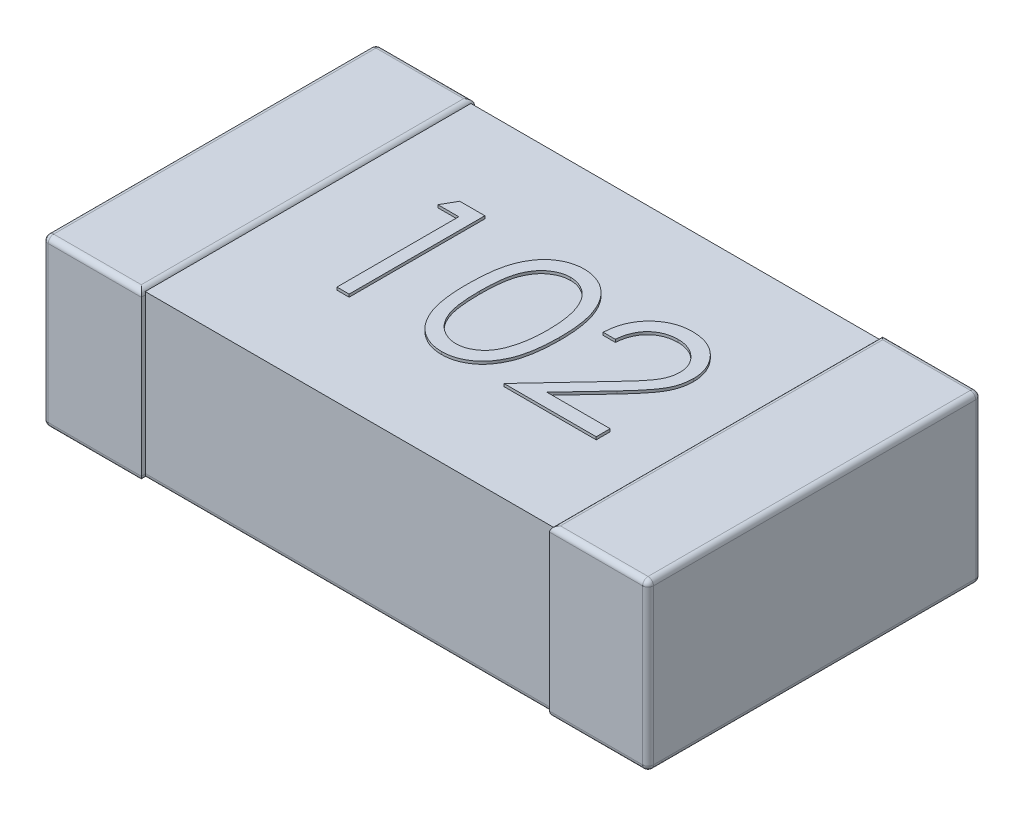
SolidWorks part; units mm, degrees
ref_plane "Front Plane" through (0, 0, 0) normal (0, 0, 1) x (1, 0, 0)
ref_plane "Top Plane" through (0, 0, 0) normal (0, 1, 0) x (1, 0, 0)
ref_plane "Right Plane" through (0, 0, 0) normal (1, 0, 0) x (0, 0, -1)
sketch "Sketch1" plane through (0, 0, 0) normal (0, 1, 0) x (1, 0, 0)
  line L1 (1.1, 0.6) -> (-1.1, 0.6)
  line L2 (1.1, 0.6) -> (1.1, -0.6)
  line L3 (1.1, -0.6) -> (-1.1, -0.6)
  line L4 (-1.1, 0.6) -> (-1.1, -0.6)
  line L5 (1.1, 0.6) -> (-1.1, -0.6) construction
  line L6 (1.1, -0.6) -> (-1.1, 0.6) construction
  point P0 (0, 0)
  dimension "D1" = 2.2
  dimension "D2" = 1.2
extrude "Boss-Extrude1" add sketch "Sketch1" along normal blind 0.6
sketch "Sketch2" plane through (0, 0, 0) normal (0, 1, 0) x (1, 0, 0)
  line L0 (0.7507, 0) -> (-0.7507, 0) construction
  line L1 (-1.1136, 0.6109) -> (-0.7507, 0.6109)
  line L2 (-1.1136, 0.6109) -> (-1.1136, -0.6164)
  line L3 (-1.1136, -0.6164) -> (-0.7507, -0.6164)
  line L4 (-0.7507, 0.6109) -> (-0.7507, -0.6164)
  line L5 (1.1136, 0.6137) -> (0.7507, 0.6137)
  line L6 (1.1136, 0.6137) -> (1.1136, -0.6137)
  line L7 (1.1136, -0.6137) -> (0.7507, -0.6137)
  line L8 (0.7507, 0.6137) -> (0.7507, -0.6137)
  line L9 (-1.1, 0.6) -> (-1.1, -0.6) construction
  line L10 (-1.1, -0.6) -> (1.1, -0.6) construction
  line L11 (1.1, 0.6) -> (-1.1, 0.6) construction
  point P12 (0, 0)
  dimension "D1" = 0.3493
  dimension "D2" = 2.2136
  dimension "D3" = 1.2109
  dimension "D4" = 1.2137
  dimension "D5" = 0.0109
extrude "Boss-Extrude2" add sketch "Sketch2" along normal offset from surface (0.611 mm away) 0.011 up to face at (0, 0.6, 0) offset beyond the face yes
fillet "Fillet1" radius 0.02 24 edges at (-0.7507, 0, -0.6055) (-0.9321, 0, -0.6109) (-0.9321, 0, 0.6164) (-0.7507, 0, 0.6082) (0, 0, 0.6) (0.7507, 0, 0.6068) (0.9321, 0, 0.6137) (0.9321, 0, -0.6137) (0.7507, 0, -0.6068) (0, 0, -0.6) (-1.1136, 0, 0.0027) (-1.1136, 0.3055, -0.6109) (-1.1136, 0.3055, 0.6164) (-1.1136, 0.611, 0.0027) (-0.9321, 0.611, -0.6109) (-0.7507, 0.611, 0.0027) (-0.9321, 0.611, 0.6164) (0.9321, 0.611, 0.6137) (0.7507, 0.611, 0) (0.9321, 0.611, -0.6137) (1.1136, 0, 0) (1.1136, 0.3055, 0.6137) (1.1136, 0.611, 0) (1.1136, 0.3055, -0.6137)
sketch "Sketch3" plane through (0, 0.6, 0) normal (0, 1, 0) x (1, 0, 0)
  line L0 (-0.7528, -0.2424) -> (0.7528, -0.2424) construction
  line L1 (-0.7528, 0.6) -> (-0.7528, -0.6) construction
  line L2 (0.7528, -0.6) -> (0.7528, 0.6) construction
  text T0 "102" font "Century Gothic" height 0.5
extrude "Writing" add sketch "Sketch3" along normal blind 0.01 separate body
